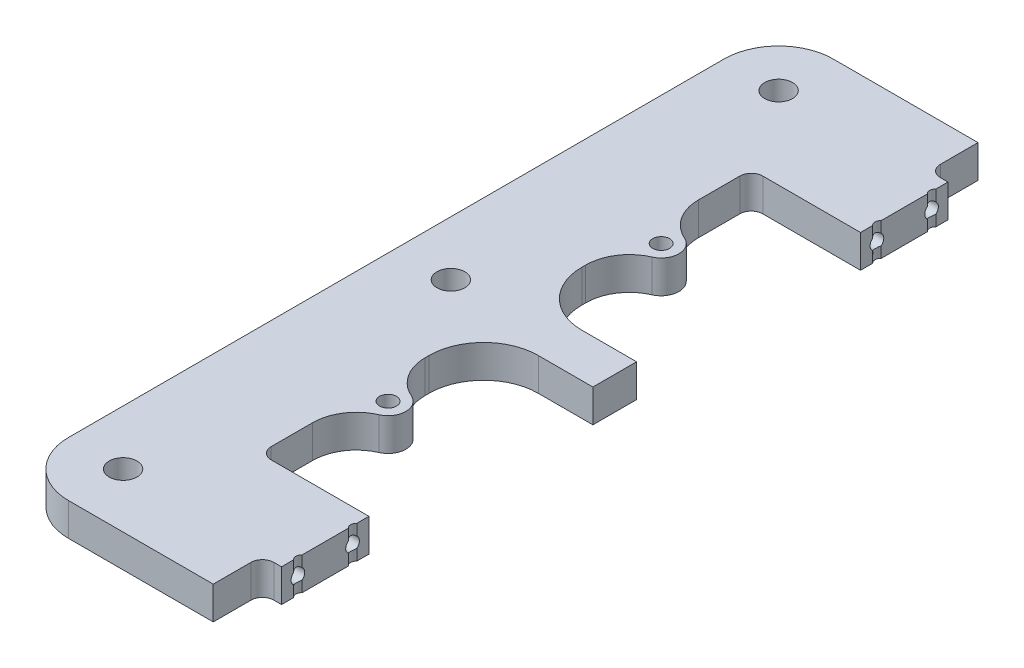
SolidWorks part; units mm, degrees
ref_plane "正面" through (0, 0, 0) normal (0, 0, 1) x (1, 0, 0)
ref_plane "平面" through (0, 0, 0) normal (0, 1, 0) x (1, 0, 0)
ref_plane "右側面" through (0, 0, 0) normal (1, 0, 0) x (0, 0, -1)
sketch "ｽｹｯﾁ1" plane through (0, 0, 0) normal (0, 1, 0) x (1, 0, 0)
  line L0 (0, -70) -> (0, 70)
  line L1 (0, 70) -> (36.5, 70)
  line L2 (36.5, 70) -> (36.5, 61)
  line L3 (36.5, 61) -> (40, 61)
  line L4 (40, 61) -> (40, 45)
  line L5 (40, 45) -> (20, 45)
  line L6 (20, 45) -> (20, -45)
  line L7 (20, 0) -> (0, 0) construction
  line L8 (40, -45) -> (20, -45)
  line L9 (40, -61) -> (40, -45)
  line L10 (36.5, -61) -> (40, -61)
  line L11 (36.5, -70) -> (36.5, -61)
  line L12 (0, -70) -> (36.5, -70)
  dimension "D1" = 140
  dimension "D2" = 9
  dimension "D3" = 3.5
  dimension "D4" = 25
  dimension "D5" = 40
  dimension "D6" = 20
extrude "ﾎﾞｽ - 押し出し1" add sketch "ｽｹｯﾁ1" along normal blind 6
sketch "ｽｹｯﾁ2" plane through (40, 0, 0) normal (1, 0, 0) x (0, 0, -1)
  line L0 (65, 6) -> (65, 0) construction
  line L1 (61, 6) -> (70, 6) construction
  line L2 (61, 0) -> (70, 0) construction
  line L3 (48, 6) -> (48, 0) construction
  line L4 (45, 6) -> (61, 6) construction
  line L5 (45, 0) -> (61, 0) construction
  line L6 (70, 6) -> (70, 0) construction
  line L7 (0, 0) -> (0, 6) construction
  line L8 (-45, 6) -> (45, 6) construction
  line L9 (58, 6) -> (58, 0) construction
  line L10 (53, 6) -> (53, 0) construction
  line L11 (48, 3) -> (53, 3) construction
  line L12 (53, 3) -> (58, 3) construction
  circle A0 centre (65, 3) radius 1.25 construction
  circle A1 centre (48, 3) radius 1.25
  circle A2 centre (58, 3) radius 1.25
  circle A3 centre (-48, 3) radius 1.25
  circle A4 centre (-58, 3) radius 1.25
  circle A5 centre (-65, 3) radius 1.25 construction
  dimension "D1" = 2.5
  dimension "D2" = 2.5
  dimension "D5" = 2.5
  dimension "D3" = 22
  dimension "D4" = 5
extrude "ｶｯﾄ - 押し出し1" cut sketch "ｽｹｯﾁ2" against normal blind 10
sketch "ｽｹｯﾁ3" plane through (0, 6, 0) normal (0, 1, 0) x (1, 0, 0)
  line L0 (36.5, 65) -> (37.2, 65) construction
  line L1 (36.5, 61) -> (36.5, 70) construction
  line L2 (40, 48) -> (40.7, 48) construction
  line L3 (40.7, 58) -> (40, 58) construction
  line L4 (40, 45) -> (40, 61) construction
  line L5 (36.5, 70) -> (0, 70) construction
  line L6 (40, 53) -> (40.7, 53) construction
  line L7 (40, 58) -> (40, 53) construction
  line L8 (40, 53) -> (40, 48) construction
  line L9 (0, 0) -> (20, 0) construction
  line L10 (20, -45) -> (20, 45) construction
  circle A0 centre (37.2, 65) radius 1.05 construction
  circle A1 centre (40.7, 58) radius 1.05
  circle A2 centre (40.7, 48) radius 1.05
  circle A3 centre (40.7, -48) radius 1.05
  circle A4 centre (40.7, -58) radius 1.05
  circle A5 centre (37.2, -65) radius 1.05 construction
  dimension "D3" = 2.1
  dimension "D1" = 5
  dimension "D2" = 22
  dimension "D4" = 0.7
extrude "ｶｯﾄ - 押し出し2" cut sketch "ｽｹｯﾁ3" against normal through all
sketch "ｽｹｯﾁ4" plane through (0, 6, 0) normal (0, 1, 0) x (1, 0, 0)
  line L0 (10, 70) -> (10, -70) construction
  line L1 (36.5, 70) -> (0, 70) construction
  line L2 (0, -70) -> (36.5, -70) construction
  line L3 (0, 0) -> (10, 0) construction
  line L4 (10, 0) -> (20, 0) construction
  line L5 (20, -45) -> (20, 45) construction
  circle A0 centre (10, 0) radius 2.55
  circle A1 centre (10, 60) radius 2.55
  circle A2 centre (10, -60) radius 2.55
  point P17 (10, -46.6019)
  dimension "D1" = 5.1
  dimension "D2" = 10
  dimension "D3" = 10
extrude "ｶｯﾄ - 押し出し3" cut sketch "ｽｹｯﾁ4" against normal through all
fillet "ﾌｨﾚｯﾄ1" radius 2.1 4 edges at (36.5, 3, -61) (20, 3, -45) (20, 3, 45) (36.5, 3, 61)
sketch "ｽｹｯﾁ5" plane through (20, 0, 0) normal (1, 0, 0) x (0, 0, -1)
  line L0 (-42.9, 0) -> (42.9, 0) construction
  line L1 (-4, 6) -> (4, 6)
  line L2 (-4, 6) -> (-4, 0)
  line L3 (-4, 0) -> (4, 0)
  line L4 (4, 6) -> (4, 0)
  line L5 (-4, 6) -> (4, 0) construction
  line L6 (-4, 0) -> (4, 6) construction
  line L7 (-42.9, 6) -> (42.9, 6) construction
  point P0 (0, 3)
  point P9 (0, 0)
  dimension "D1" = 8
extrude "ﾎﾞｽ - 押し出し2" add sketch "ｽｹｯﾁ5" along normal up to surface (20 mm away) up to face at (40, 3, -53)
fillet "ﾌｨﾚｯﾄ2" radius 10 2 edges at (20, 3, 4) (20, 3, -4)
fillet "ﾌｨﾚｯﾄ3" radius 10 2 edges at (0, 3, 70) (0, 3, -70)
sketch "ｽｹｯﾁ7" plane through (0, 6, 0) normal (0, 1, 0) x (1, 0, 0)
  line L0 (0, 0) -> (40, 0) construction
  line L1 (0, 60) -> (0, -60) construction
  line L2 (40, -4) -> (40, 4) construction
  line L3 (0, 25) -> (40.5945, 25) construction
  line L4 (23.5, 28.25) -> (20, 28.25)
  line L5 (20, 14) -> (20, 42.9) construction
  line L6 (20, 28.25) -> (20, 21.75)
  line L7 (20, 21.75) -> (23.5, 21.75)
  line L8 (0, -25) -> (40.5945, -25) construction
  line L9 (20, -21.75) -> (23.5, -21.75)
  line L10 (20, -28.25) -> (20, -21.75)
  line L11 (23.5, -28.25) -> (20, -28.25)
  circle A0 centre (23.5, 25) radius 1.55
  arc A1 (23.5, 28.25) -> (23.5, 21.75) centre (23.5, 25) cw
  arc A2 (23.5, -28.25) -> (23.5, -21.75) centre (23.5, -25) ccw
  circle A3 centre (23.5, -25) radius 1.55
  dimension "D1" = 3.1
  dimension "D2" = 6.5
  dimension "D3" = 3.5
  dimension "D4" = 25
extrude "ﾎﾞｽ - 押し出し3" add sketch "ｽｹｯﾁ7" against normal through all
fillet "ﾌｨﾚｯﾄ4" radius 8 4 edges at (20, 3, 28.25) (20, 3, 21.75) (20, 3, -28.25) (20, 3, -21.75)
